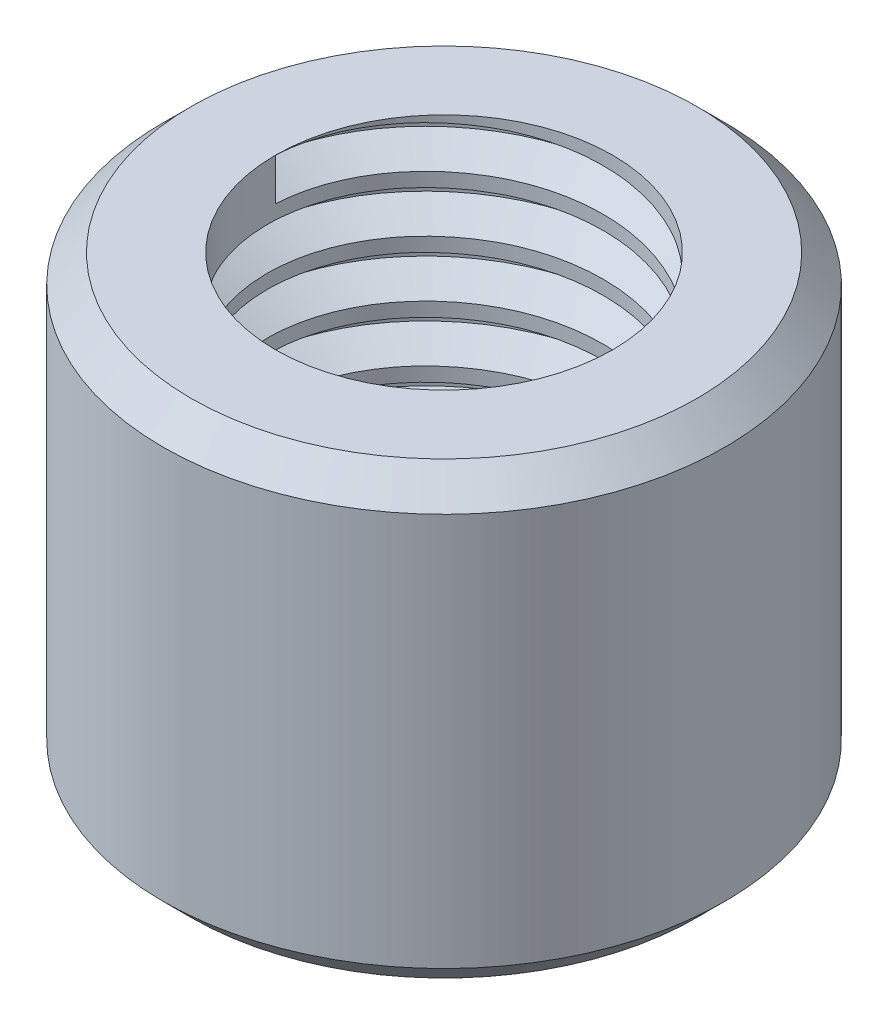
SolidWorks part; units mm, degrees
ref_plane "Front Plane" through (0, 0, 0) normal (0, 0, 1) x (1, 0, 0)
ref_plane "Top Plane" through (0, 0, 0) normal (0, 1, 0) x (1, 0, 0)
ref_plane "Right Plane" through (0, 0, 0) normal (1, 0, 0) x (0, 0, -1)
sketch "Sketch1" plane through (0, 0, 0) normal (0, 1, 0) x (1, 0, 0)
  circle A0 centre (0, 0) radius 2.5
  circle A1 centre (0, 0) radius 1.5
  dimension "D1" = 3
  dimension "D2" = 5
extrude "Boss-Extrude1" add sketch "Sketch1" along normal blind 4
chamfer "Chamfer1" distance 0.25 angle 45 2 edges at (0, 0, 2.5) (0, 4, 2.5)
thread "Thread1" pitch 0.5 method cut profile "Thread Profile1" start angle 0, offset 0, length 4.5, pitch 0.5, diameter 3
ref_plane "Plane1" through (-1.5, 4, 0) normal (0, 0, 1) x (-1, 0, 0)
sketch "Thread Profile1" plane through (-1.5, 4, 0) normal (0, 0, 1) x (-1, 0, 0)
  line L0 (0, 0) -> (0, 0.5) construction
  line L1 (0, 0) -> (0.2706, 0.1562)
  line L2 (0.2706, 0.1562) -> (0.2706, 0.2187)
  line L3 (0.2706, 0.2187) -> (0, 0.375)
  line L4 (0.2706, 0.1875) -> (0, 0.1875) construction
  line L11 (0, 0) -> (0, 0.375)
  point P2 (0, 0)
  dimension "Pitch" = 0.5
  dimension "Profile_Angle" = 60
  dimension "Profile_Land" = 0.0625
  dimension "Profile_Height" = 0.2706
